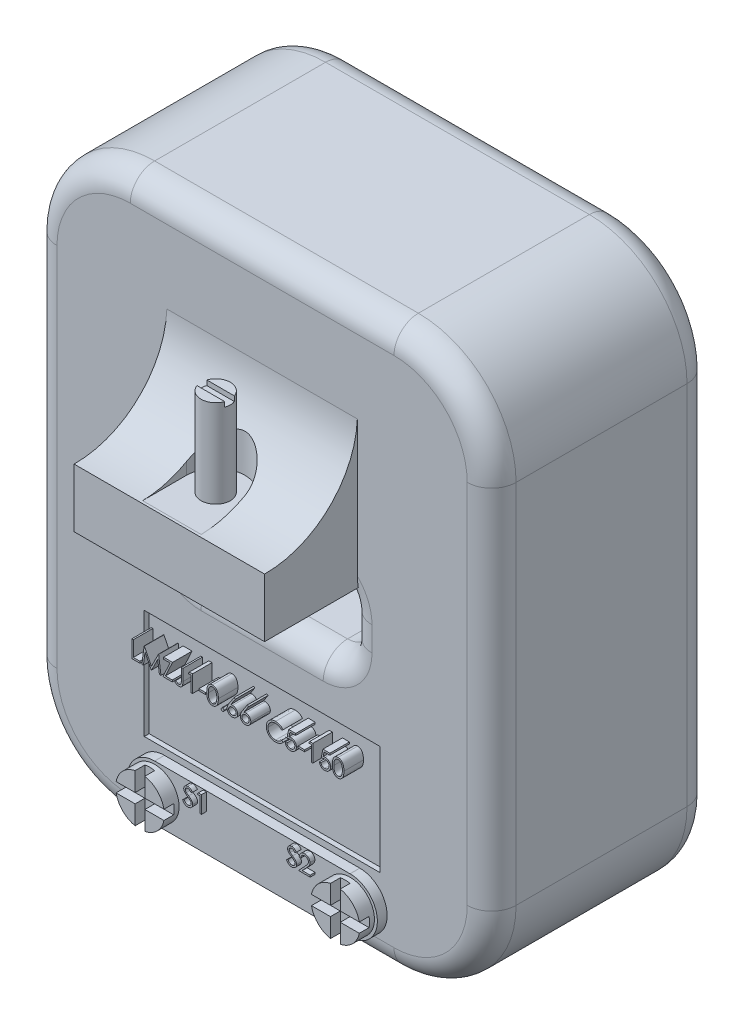
SolidWorks part; units mm, degrees
ref_plane "前视基准面" through (0, 0, 0) normal (0, 0, 1) x (1, 0, 0)
ref_plane "上视基准面" through (0, 0, 0) normal (0, 1, 0) x (1, 0, 0)
ref_plane "右视基准面" through (0, 0, 0) normal (1, 0, 0) x (0, 0, -1)
sketch "草图1" plane through (0, 0, 0) normal (0, 0, 1) x (1, 0, 0)
  line L0 (0, 57.5) -> (0, -57.5) construction
  line L1 (-27, 57.5) -> (27, 57.5)
  line L2 (-47, 37.5) -> (-47, -37.5)
  line L3 (-27, -57.5) -> (27, -57.5)
  line L4 (47, 37.5) -> (47, -37.5)
  line L5 (-47, 57.5) -> (47, -57.5) construction
  line L6 (-47, -57.5) -> (47, 57.5) construction
  line L7 (-12.5, 7.5) -> (12.5, 7.5)
  line L8 (-17.5, 2.5) -> (-17.5, -2.5)
  line L9 (-12.5, -7.5) -> (12.5, -7.5)
  line L10 (17.5, 2.5) -> (17.5, -2.5)
  line L11 (-17.5, 7.5) -> (17.5, -7.5) construction
  line L12 (-17.5, -7.5) -> (17.5, 7.5) construction
  line L13 (-19, -38.3962) -> (-21, -38.3962)
  line L14 (-24.1327, -40.6229) -> (24.1327, -40.6229)
  line L15 (-24.1327, -40.6229) -> (-24.1327, -18.2502)
  line L16 (-24.1327, -18.2502) -> (24.1327, -18.2502)
  line L17 (24.1327, -40.6229) -> (24.1327, -18.2502)
  line L18 (-24.1327, -40.6229) -> (24.1327, -18.2502) construction
  line L19 (-24.1327, -18.2502) -> (24.1327, -40.6229) construction
  line L20 (8.8169, -46.5) -> (31.1831, -46.5)
  line L21 (8.8169, -46.5) -> (8.8169, -48.5)
  line L22 (8.8169, -48.5) -> (31.1831, -48.5)
  line L23 (31.1831, -46.5) -> (31.1831, -48.5)
  line L24 (8.8169, -46.5) -> (31.1831, -48.5) construction
  line L25 (8.8169, -48.5) -> (31.1831, -46.5) construction
  line L26 (19, -56.6038) -> (21, -56.6038)
  line L27 (19, -56.6038) -> (19, -38.3962)
  line L28 (19, -38.3962) -> (21, -38.3962)
  line L29 (21, -56.6038) -> (21, -38.3962)
  line L30 (19, -56.6038) -> (21, -38.3962) construction
  line L31 (19, -38.3962) -> (21, -56.6038) construction
  line L32 (-19, -56.6038) -> (-21, -56.6038)
  line L33 (-21, -56.6038) -> (-21, -38.3962)
  line L34 (-19, -56.6038) -> (-19, -38.3962)
  line L35 (-8.8169, -46.5) -> (-8.8169, -48.5)
  line L36 (-8.8169, -46.5) -> (-31.1831, -46.5)
  line L37 (-31.1831, -46.5) -> (-31.1831, -48.5)
  line L38 (-8.8169, -48.5) -> (-31.1831, -48.5)
  line L39 (-20, -41.9) -> (20, -41.9)
  line L40 (-20, -53.1) -> (20, -53.1)
  arc A0 (47, -37.5) -> (27, -57.5) centre (27, -37.5) cw
  circle A1 centre (20, -47.5) radius 5
  circle A2 centre (-20, -47.5) radius 5
  arc A3 (-20, -53.1) -> (-20, -41.9) centre (-20, -47.5) cw
  arc A4 (20, -53.1) -> (20, -41.9) centre (20, -47.5) ccw
  arc A5 (-47, -37.5) -> (-27, -57.5) centre (-27, -37.5) ccw
  arc A6 (47, 37.5) -> (27, 57.5) centre (27, 37.5) ccw
  arc A7 (-27, 57.5) -> (-47, 37.5) centre (-27, 37.5) ccw
  arc A8 (-12.5, 7.5) -> (-17.5, 2.5) centre (-12.5, 2.5) ccw
  arc A9 (-12.5, -7.5) -> (-17.5, -2.5) centre (-12.5, -2.5) cw
  arc A10 (12.5, 7.5) -> (17.5, 2.5) centre (12.5, 2.5) cw
  arc A11 (17.5, -2.5) -> (12.5, -7.5) centre (12.5, -2.5) cw
  point P0 (0, 0)
  point P6 (0, 0)
  point P13 (0, -29.4366)
  dimension "D8" = 20
  dimension "D9" = 5
  dimension "D11" = 10
  dimension "D12" = 5.6
  dimension "D1" = 115
  dimension "D2" = 94
  dimension "D3" = 35
  dimension "D4" = 15
  dimension "D5" = 20
  dimension "D6" = 2
  dimension "D7" = 2
  dimension "D10" = 10
extrude "凸台-拉伸1" add sketch "草图1" against normal blind 45 contours A11 L10 A10 L7 A8 L8 A9 L9 | L4 A0 L3 A5 L2 A7 L1 A6 region at (0, 0, 0)
fillet "圆角1" radius 5 32 edges at (0, -7.5, -45) (-16.0355, -6.0355, -45) (-17.5, 0, -45) (-16.0355, 6.0355, -45) (0, 7.5, -45) (16.0355, 6.0355, -45) (17.5, 0, -45) (16.0355, -6.0355, -45) (0, 57.5, -45) (-41.1421, 51.6421, -45) (-47, 0, -45) (-41.1421, -51.6421, -45) (0, -57.5, -45) (41.1421, -51.6421, -45) (47, 0, -45) (41.1421, 51.6421, -45) (16.0355, 6.0355, 0) (0, 7.5, 0) (-16.0355, 6.0355, 0) (-17.5, 0, 0) (-16.0355, -6.0355, 0) (0, -7.5, 0) (16.0355, -6.0355, 0) (17.5, 0, 0) (47, 0, 0) (41.1421, -51.6421, 0) (0, -57.5, 0) (-41.1421, -51.6421, 0) (-47, 0, 0) (-41.1421, 51.6421, 0) (0, 57.5, 0) (41.1421, 51.6421, 0)
extrude "凸台-拉伸2" add sketch "草图1<3>" along normal blind 2 contours L40 A4 L39 A3
sketch "草图1<3>" plane through (0, 0, 0) normal (0, 0, 1) x (1, 0, 0) same geometry as "草图1"
extrude "凸台-拉伸3" add sketch "草图1<4>" along normal blind 5 contours A2 | A1
sketch "草图1<4>" plane through (0, 0, 0) normal (0, 0, 1) x (1, 0, 0) same geometry as "草图1"
extrude "切除-拉伸1" cut sketch "草图1<5>" against normal blind 2 from offset 5 contours L36 L37 L38 L35 | L34 L13 L33 L32 | L27 L28 L29 L26 | L20 L23 L22 L21
sketch "草图1<5>" plane through (0, 0, 0) normal (0, 0, 1) x (1, 0, 0) same geometry as "草图1"
extrude "切除-拉伸2" cut sketch "草图1<7>" against normal blind 1 contours L14 L17 L16 L15
sketch "草图1<7>" plane through (0, 0, 0) normal (0, 0, 1) x (1, 0, 0) same geometry as "草图1"
sketch "草图3" plane through (0, 0, 0) normal (1, 0, 0) x (0, 0, -1)
  line L0 (40, 7.5) -> (5, 7.5) construction
  line L1 (40, 7.5) -> (5, 7.5)
  line L2 (5, 7.5) -> (-19, 7.5)
  line L3 (-19, 7.5) -> (-19, 19.5)
  line L4 (0, 12.5) -> (0, 37.5)
  line L5 (22.5, 57.5) -> (22.5, -7.5) construction
  line L6 (40, 57.5) -> (5, 57.5) construction
  line L7 (40, -7.5) -> (5, -7.5) construction
  line L8 (45, 12.5) -> (45, 37.5)
  line L9 (40, 7.5) -> (64, 7.5)
  line L10 (64, 7.5) -> (64, 19.5)
  arc A0 (-19, 19.5) -> (0, 37.5) centre (-18.7367, 38.2498) ccw
  arc A1 (0, 12.5) -> (5, 7.5) centre (5, 12.5) ccw construction
  arc A2 (0, 12.5) -> (5, 7.5) centre (5, 12.5) ccw
  arc A3 (45, 12.5) -> (40, 7.5) centre (40, 12.5) cw
  arc A4 (64, 19.5) -> (45, 37.5) centre (63.7367, 38.2498) cw
  dimension "D1" = 12
  dimension "D2" = 19
extrude "凸台-拉伸4" add sketch "草图3" along normal blind 19.5 and the other way blind 19.5 contours A2 L4 A0 L3 L2 | L9 L10 A4 L8 A3 region at (0, 15.8925, 8.021)
sketch "草图4" plane through (0, 7.5, 0) normal (0, -1, 0) x (1, 0, 0)
  line L0 (0, 29.074) -> (0, -77.0247) construction
  line L1 (-4.7685, -53.5) -> (4.7685, -55.5) construction
  line L4 (-6, 9.5) -> (-6, 29.074)
  line L5 (-6, 29.074) -> (6, 29.074)
  line L6 (6, 29.074) -> (6, 9.5)
  line L7 (-27, -22.5) -> (27, -22.5) construction
  line L8 (-4.7685, 10.5) -> (4.7685, 10.5)
  line L9 (-4.7685, 10.5) -> (-4.7685, 8.5)
  line L10 (-4.7685, 8.5) -> (4.7685, 8.5)
  line L11 (4.7685, 10.5) -> (4.7685, 8.5)
  line L12 (-4.7685, 10.5) -> (4.7685, 8.5) construction
  line L13 (-4.7685, 8.5) -> (4.7685, 10.5) construction
  line L14 (-27, -40) -> (-27, -5) construction
  line L15 (27, -40) -> (27, -5) construction
  line L16 (-4.7685, -55.5) -> (4.7685, -53.5) construction
  line L17 (4.7685, -55.5) -> (4.7685, -53.5)
  line L18 (-4.7685, -53.5) -> (4.7685, -53.5)
  line L19 (-4.7685, -55.5) -> (-4.7685, -53.5)
  line L20 (-4.7685, -55.5) -> (4.7685, -55.5)
  line L21 (6, -74.074) -> (6, -54.5)
  line L22 (-6, -74.074) -> (6, -74.074)
  line L23 (-6, -54.5) -> (-6, -74.074)
  arc A0 (-6, 9.5) -> (6, 9.5) centre (0, 9.5) ccw
  circle A1 centre (0, 9.5) radius 3
  circle A2 centre (0, -54.5) radius 3
  arc A3 (-6, -54.5) -> (6, -54.5) centre (0, -54.5) cw
  dimension "D1" = 12
  dimension "D2" = 6
  dimension "D3" = 2
  dimension "D4" = 32
extrude "切除-拉伸3" cut sketch "草图4" against normal blind 39 from offset 12 contours L4 L5 L6 A0 | L23 L22 L21 A3 offset against normal yes
extrude "凸台-拉伸5" add sketch "草图4<3>" against normal blind 30 and the other way blind 6 contours A2 | A1
sketch "草图4<3>" plane through (0, 7.5, 0) normal (0, -1, 0) x (1, 0, 0) same geometry as "草图4"
sketch "草图5" plane through (0, 0, 0) normal (0, 0, 1) x (1, 0, 0)
  text T0 "\r\nLMZJ1-0.66  C5-150\r\n\r\n\r\n        S1            S2"
extrude "凸台-拉伸6" add sketch "草图5" along normal blind 3 and the other way blind 1
extrude "切除-拉伸4" cut sketch "草图4<4>" along normal blind 1 from offset 30 contours L20 L17 L18 L19 | L9 L10 L11 L8 offset against normal yes
sketch "草图4<4>" plane through (0, 7.5, 0) normal (0, -1, 0) x (1, 0, 0) same geometry as "草图4"
sketch "草图6" plane through (0, 0, 3) normal (0, 0, 1) x (1, 0, 0)
  point P0 (19.7205, -47.3136)
  point P1 (-20, -47.5)
sketch "0_0_Point" plane through (0, 0, 3) normal (0, 0, 1) x (1, 0, 0)
  point P0 (-20, -47.5)
other "0_0" parameters "直径"=2, "端头长度"=2
ref_axis "基准轴1" through (-20, -47.5, 13) along (0, 0, -1)
sketch "0_1_Point" plane through (0, 0, 3) normal (0, 0, 1) x (1, 0, 0)
  point P0 (19.7205, -47.3136)
other "0_1" parameters "直径"=2, "端头长度"=2
ref_axis "基准轴2" through (19.7205, -47.3136, 13) along (0, 0, -1)
